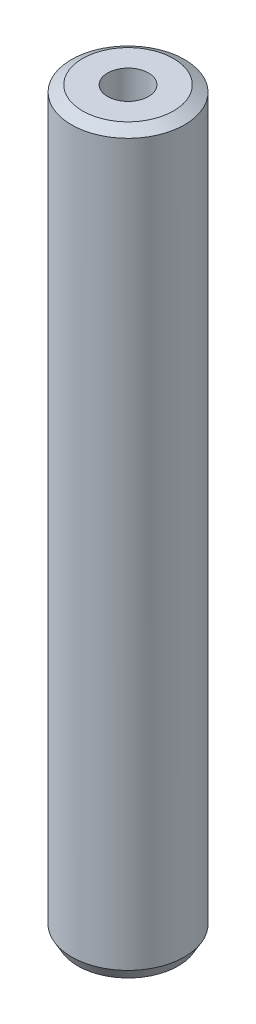
SolidWorks part; units mm, degrees
ref_plane "Front Plane" through (0, 0, 0) normal (0, 0, 1) x (1, 0, 0)
ref_plane "Top Plane" through (0, 0, 0) normal (0, 1, 0) x (1, 0, 0)
ref_plane "Right Plane" through (0, 0, 0) normal (1, 0, 0) x (0, 0, -1)
sketch "Sketch1" plane through (0, 0, 0) normal (0, 1, 0) x (1, 0, 0)
  circle A0 centre (0, 0) radius 7.5
  dimension "SHAFT_OD" = 15
extrude "Boss-Extrude1" add sketch "Sketch1" along normal blind 97.8375
sketch "Sketch2" plane through (0, 0, 0) normal (0, 1, 0) x (1, 0, 0)
  circle A0 centre (0, 0) radius 2.7108
  dimension "BORE_D" = 5.4215
extrude "Cut-Extrude1" cut sketch "Sketch2" along normal through all
chamfer "Chamfer1" distance 0.8505 angle 60 2 edges at (0, 97.8375, 7.5) (0, 0, 7.5) first distance on face at (0, 97.8375, 7.5) first distance on face at (0, 0, 2.7108)
